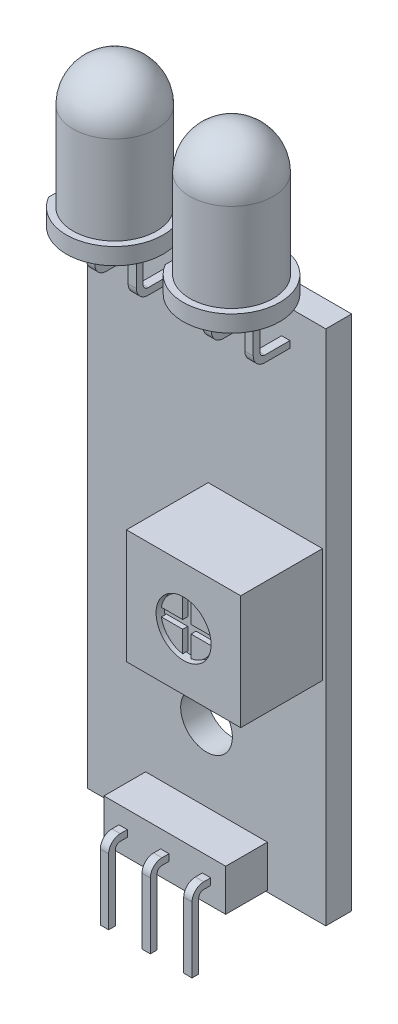
SolidWorks part; units mm, degrees
ref_plane "Plano frontal" through (0, 0, 0) normal (0, 0, 1) x (1, 0, 0)
ref_plane "Plano superior" through (0, 0, 0) normal (0, 1, 0) x (1, 0, 0)
ref_plane "Plano direito" through (0, 0, 0) normal (1, 0, 0) x (0, 0, -1)
sketch "Esboço1" plane through (0, 0, 0) normal (0, 0, 1) x (1, 0, 0)
  line L1 (7.15, 15.5) -> (-7.15, 15.5)
  line L2 (7.15, 15.5) -> (7.15, -15.5)
  line L3 (7.15, -15.5) -> (-7.15, -15.5)
  line L4 (-7.15, 15.5) -> (-7.15, -15.5)
  line L5 (7.15, 15.5) -> (-7.15, -15.5) construction
  line L6 (7.15, -15.5) -> (-7.15, 15.5) construction
  circle A0 centre (0, -8.5) radius 1.55
  point P0 (0, 0)
  dimension "D4" = 3.1
  dimension "D1" = 14.3
  dimension "D2" = 31
  dimension "D3" = 7
extrude "Ressalto-extrusão1" add sketch "Esboço1" along normal blind 1.55
sketch "Esboço2" plane through (0, 0, 0) normal (0, 0, 1) x (1, 0, 0)
  line L0 (7.15, -15.5) -> (7.15, 15.5) construction
  line L1 (6.95, 3.9915) -> (0.1, 3.9915)
  line L2 (6.95, 3.9915) -> (6.95, -2.8585)
  line L3 (6.95, -2.8585) -> (0.1, -2.8585)
  line L4 (0.1, 3.9915) -> (0.1, -2.8585)
  dimension "D1" = 6.85
  dimension "D2" = 6.85
  dimension "D3" = 0.2
extrude "Ressalto-extrusão2" add sketch "Esboço2" along normal blind 6.45
sketch "Esboço3" plane through (0, 0, 6.45) normal (0, 0, 1) x (1, 0, 0)
  line L0 (0.1, -2.8585) -> (3.275, 0.3165) construction
  line L1 (3.775, 0.8165) -> (3.775, 2.0962)
  line L3 (3.775, -0.9632) -> (3.775, 0.3165)
  line L5 (3.275, -0.9632) -> (3.275, 0.3165)
  line L8 (5.0547, 0.3165) -> (3.775, 0.3165)
  line L10 (5.0547, 0.8165) -> (3.775, 0.8165)
  line L14 (3.775, 0.8165) -> (6.95, 3.9915) construction
  line L17 (3.275, 0.8165) -> (3.275, 2.0962)
  line L24 (3.275, 0.8165) -> (1.9953, 0.8165)
  line L25 (3.275, 0.3165) -> (1.9953, 0.3165)
  circle A0 centre (3.525, 0.5665) radius 1.65
  arc A1 (1.9953, 0.3165) -> (3.275, -0.9632) centre (3.525, 0.5665) ccw
  arc A2 (3.775, -0.9632) -> (5.0547, 0.3165) centre (3.525, 0.5665) ccw
  arc A3 (5.0547, 0.8165) -> (3.775, 2.0962) centre (3.525, 0.5665) ccw
  arc A4 (3.275, 2.0962) -> (1.9953, 0.8165) centre (3.525, 0.5665) ccw
  dimension "D1" = 3.3
  dimension "D2" = 0.1
extrude "Corte-extrusão1" cut sketch "Esboço3" against normal blind 0.5
sketch "Esboço4" plane through (0, 0, 0) normal (0, 0, 1) x (1, 0, 0)
  line L2 (-3.65, -15.4) -> (-3.65, -12.9)
  line L3 (-3.65, -12.9) -> (3.65, -12.9)
  line L4 (3.65, -15.4) -> (3.65, -12.9)
  line L5 (0, -15.4) -> (0, -14.5169) construction
  line L6 (0, -15.4) -> (0, -11.5262) construction
  line L7 (-3.65, -15.4) -> (3.65, -15.4)
  line L8 (-7.15, -15.5) -> (7.15, -15.5) construction
  dimension "D1" = 7.3
  dimension "D2" = 0.1
  dimension "D3" = 2.5
extrude "Ressalto-extrusão3" add sketch "Esboço4" along normal blind 4.05
ref_plane "Plano1" through (0, 16.5, 0) normal (0, 1, 0) x (1, 0, 0)
sketch "Esboço5" plane through (0, 16.5, 0) normal (0, 1, 0) x (1, 0, 0)
  line L0 (3.5, -3.55) -> (-3.5, -3.55) construction
  line L1 (0, -3.55) -> (0, -2.346) construction
  line L2 (7.15, -1.55) -> (-7.15, -1.55) construction
  line L3 (1, -5.0197) -> (1, -2.0803)
  line L5 (-6, -2.0803) -> (-6, -5.0197)
  arc A0 (1, -5.0197) -> (1, -2.0803) centre (3.5, -3.55) ccw
  arc A1 (-6, -5.0197) -> (-6, -2.0803) centre (-3.5, -3.55) ccw
  point P4 (0, -3.55)
  dimension "D1" = 5.8
  dimension "D2" = 5.8
  dimension "D3" = 7
  dimension "D4" = 2
  dimension "D5" = 2.5
  dimension "D6" = 2.5
extrude "Ressalto-extrusão4" add sketch "Esboço5" along normal blind 1 separate body
sketch "Esboço6" plane through (0, 16.5, 0) normal (0, 1, 0) x (1, 0, 0)
  circle A0 centre (3.5, -3.55) radius 2.5
  circle A1 centre (-3.5, -3.55) radius 2.5
  dimension "D1" = 5
  dimension "D2" = 5
extrude "Ressalto-extrusão5" add sketch "Esboço6" along normal blind 8.8
fillet "Filete1" radius 2.5 1 edges at (-3.5, 25.3, 6.05)
fillet "Filete2" radius 2.5 1 edges at (3.5, 25.3, 6.05)
sketch "Esboço7" plane through (-7.15, 0, 0) normal (-1, 0, 0) x (0, 0, 1)
  line L0 (3.55, 16.5) -> (3.55, 14.117) construction
  line L1 (2.0803, 16.5) -> (5.0197, 16.5) construction
  line L2 (3.05, 13.617) -> (1.55, 13.617) construction
  line L3 (1.55, 15.5) -> (1.55, -15.5) construction
  line L4 (3.35, 16.5) -> (3.35, 14.117)
  line L5 (3.05, 13.817) -> (1.55, 13.817)
  line L6 (3.75, 16.5) -> (3.75, 14.117)
  line L7 (3.05, 13.417) -> (1.55, 13.417)
  line L8 (3.35, 16.5) -> (3.75, 16.5)
  line L9 (1.55, 13.817) -> (1.55, 13.417)
  arc A0 (3.55, 14.117) -> (3.05, 13.617) centre (3.05, 14.117) cw construction
  arc A1 (3.35, 14.117) -> (3.05, 13.817) centre (3.05, 14.117) cw
  arc A2 (3.75, 14.117) -> (3.05, 13.417) centre (3.05, 14.117) cw
  dimension "D1" = 0.5
  dimension "D2" = 0.2
  dimension "D3" = 0.2
extrude "Ressalto-extrusão6" add sketch "Esboço7" against normal blind 13.8
sketch "Esboço9" plane through (0, 0, 6.45) normal (0, 0, 1) x (1, 0, 0)
  circle A0 centre (3.525, 0.5665) radius 1.55
extrude "Corte-extrusão3" cut sketch "Esboço9" against normal blind 0.2
sketch "Esboço8" plane through (0, 0, 3.75) normal (0, 0, 1) x (1, 0, 0)
  line L0 (-3.5, 22.8) -> (-3.5, 9.1384) construction
  line L1 (-1, 22.8) -> (-6, 22.8) construction
  line L2 (-0.6069, 16.5) -> (-6, 16.5) construction
  line L3 (6, 22.8) -> (1, 22.8) construction
  line L4 (3.5, 22.8) -> (3.5, 9.1384) construction
  line L5 (-8.5365, 16.5) -> (-5, 16.5)
  line L6 (-8.5365, 16.5) -> (-8.5365, 10.1677)
  line L7 (-8.5365, 10.1677) -> (-5, 10.1677)
  line L8 (-5, 16.5) -> (-5, 10.1677)
  line L9 (-4.5, 16.5) -> (-2.5, 16.5)
  line L10 (-4.5, 16.5) -> (-4.5, 10.1677)
  line L11 (-4.5, 10.1677) -> (-2.5, 10.1677)
  line L12 (-2.5, 16.5) -> (-2.5, 10.1677)
  line L14 (7.0966, 16.5) -> (5, 16.5)
  line L15 (7.0966, 16.5) -> (7.0966, 10.1677)
  line L16 (7.0966, 10.1677) -> (5, 10.1677)
  line L17 (5, 16.5) -> (5, 10.1677)
  line L19 (1, 16.5) -> (6.3931, 16.5) construction
  line L20 (2.5, 16.5) -> (4.5, 16.5)
  line L21 (2.5, 16.5) -> (2.5, 10.9232)
  line L22 (2.5, 10.9232) -> (4.5, 10.9232)
  line L23 (4.5, 16.5) -> (4.5, 10.9232)
  line L25 (-2, 16.5) -> (2, 16.5)
  line L26 (-2, 16.5) -> (-2, 10.1677)
  line L27 (-2, 10.1677) -> (2, 10.1677)
  line L28 (2, 16.5) -> (2, 10.1677)
  dimension "D1" = 1
  dimension "D2" = 0.5
  dimension "D3" = 0.5
  dimension "D4" = 1
  dimension "D5" = 1
  dimension "D6" = 1
  dimension "D7" = 0.5
  dimension "D8" = 0.5
extrude "Corte-extrusão2" cut sketch "Esboço8" against normal up to surface (2.2 mm away) and the other way blind 10 up to face at (3.525, 0.5665, 1.55)
sketch "Esboço11" plane through (-3.65, 0, 0) normal (-1, 0, 0) x (0, 0, 1)
  line L0 (4.05, -14.15) -> (4.4674, -14.15) construction
  line L1 (4.05, -12.9) -> (4.05, -15.4) construction
  line L2 (4.9674, -14.65) -> (4.9674, -18.5951) construction
  line L3 (4.05, -14.35) -> (4.4674, -14.35)
  line L4 (4.7674, -14.65) -> (4.7674, -18.5951)
  line L5 (4.05, -13.95) -> (4.4674, -13.95)
  line L6 (5.1674, -14.65) -> (5.1674, -18.5951)
  line L7 (4.05, -13.95) -> (4.05, -14.35)
  line L8 (4.7674, -18.5951) -> (5.1674, -18.5951)
  arc A0 (4.4674, -14.15) -> (4.9674, -14.65) centre (4.4674, -14.65) cw construction
  arc A1 (4.4674, -14.35) -> (4.7674, -14.65) centre (4.4674, -14.65) cw
  arc A2 (4.4674, -13.95) -> (5.1674, -14.65) centre (4.4674, -14.65) cw
  dimension "D1" = 0.5
  dimension "D2" = 0.2
  dimension "D3" = 0.2
extrude "Ressalto-extrusão7" add sketch "Esboço11" against normal up to vertex (7.3 mm away) up to point (3.65, -12.9, 4.05)
sketch "Esboço12" plane through (0, 0, 4.05) normal (0, 0, 1) x (1, 0, 0)
  line L0 (0, -12.9) -> (0, -12.2965) construction
  line L1 (-4.098, -13.3768) -> (-2.75, -13.3768)
  line L2 (-4.098, -13.3768) -> (-4.098, -19.3679)
  line L3 (-4.098, -19.3679) -> (-2.75, -19.3679)
  line L4 (-2.75, -13.3768) -> (-2.75, -19.3679)
  line L5 (3.7485, -13.3768) -> (2.75, -13.3768)
  line L6 (3.7485, -13.3768) -> (3.7485, -19.3679)
  line L7 (3.7485, -19.3679) -> (2.75, -19.3679)
  line L8 (2.75, -13.3768) -> (2.75, -19.3679)
  line L9 (-2.25, -13.3768) -> (-0.25, -13.3768)
  line L10 (-2.25, -13.3768) -> (-2.25, -19.3679)
  line L11 (-2.25, -19.3679) -> (-0.25, -19.3679)
  line L12 (-0.25, -13.3768) -> (-0.25, -19.3679)
  line L13 (2.25, -13.3768) -> (0.25, -13.3768)
  line L14 (2.25, -13.3768) -> (2.25, -19.3679)
  line L15 (2.25, -19.3679) -> (0.25, -19.3679)
  line L16 (0.25, -13.3768) -> (0.25, -19.3679)
  line L17 (3.65, -12.9) -> (-3.65, -12.9) construction
  line L18 (-0.25, -13.3768) -> (0.25, -13.3768) construction
  line L19 (0, -13.3768) -> (0, -14.2114) construction
  dimension "D1" = 0.5
  dimension "D2" = 0.5
  dimension "D3" = 0.5
  dimension "D4" = 2
  dimension "D5" = 2
extrude "Corte-extrusão4" cut sketch "Esboço12" along normal blind 2.2
